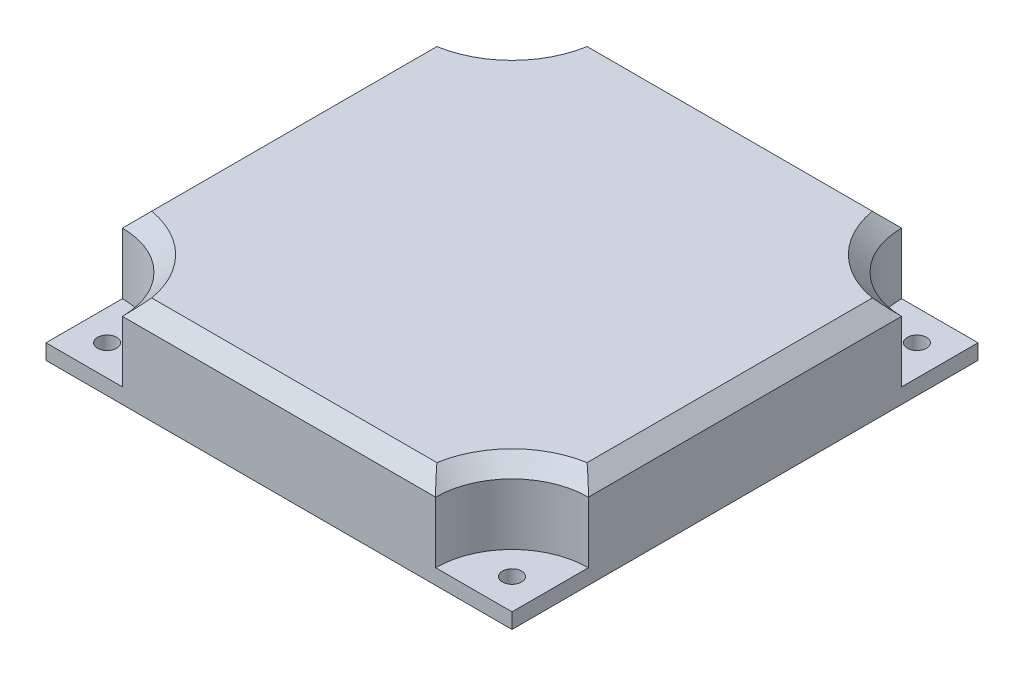
SolidWorks part; units mm, degrees
material "6061-T6 (SS)"
ref_plane "Front Plane" through (0, 0, 0) normal (0, 0, 1) x (1, 0, 0)
ref_plane "Top Plane" through (0, 0, 0) normal (0, 1, 0) x (1, 0, 0)
ref_plane "Right Plane" through (0, 0, 0) normal (1, 0, 0) x (0, 0, -1)
sketch "Sketch2" plane through (0, 0, 0) normal (0, 1, 0) x (1, 0, 0)
  line L1 (-30.5, -30.5) -> (30.5, -30.5)
  line L2 (-30.5, -30.5) -> (-30.5, 30.5)
  line L3 (-30.5, 30.5) -> (30.5, 30.5)
  line L4 (30.5, -30.5) -> (30.5, 30.5)
  line L5 (-30.5, -30.5) -> (30.5, 30.5) construction
  line L6 (-30.5, 30.5) -> (30.5, -30.5) construction
  point P0 (0, 0)
  dimension "D1" = 61
  dimension "D2" = 61
extrude "Boss-Extrude1" add sketch "Sketch2" along normal blind 12
ref_plane "Plane1" through (0, 0, 10.5) normal (0, 0, -1) x (-1, 0, 0)
ref_plane "Plane2" through (0, 0, 0) normal (1, 0, 0) x (0, 0, -1)
sketch "Sketch4" plane through (0, 12, 0) normal (0, 1, 0) x (1, 0, 0)
  line L5 (0, 0) -> (43.0078, 0) construction
  circle A1 centre (30.5, -30.5) radius 10
  circle A2 centre (-30.5, -30.5) radius 10
  circle A3 centre (-30.5, 30.5) radius 10
  circle A4 centre (30.5, 30.5) radius 10
  dimension "D1" = 20
extrude "Cut-Extrude3" cut sketch "Sketch4" against normal blind 10 contours A1 | A2 | A3 | A4
sketch "Sketch8" plane through (0, 0, 0) normal (0, -1, 0) x (1, 0, 0)
  line L12 (-18.6678, -28.5) -> (18.6678, -28.5)
  line L13 (-28.5, 18.6678) -> (-28.5, -18.6678)
  line L14 (18.6678, 28.5) -> (-18.6678, 28.5)
  line L15 (28.5, -18.6678) -> (28.5, 18.6678)
  line L16 (-18.6678, -28.5) -> (18.6678, -28.5)
  line L17 (-28.5, 18.6678) -> (-28.5, -18.6678)
  line L18 (18.6678, 28.5) -> (-18.6678, 28.5)
  line L19 (28.5, -18.6678) -> (28.5, 18.6678)
  arc A12 (28.5, -18.6678) -> (18.6678, -28.5) centre (30.5, -30.5) ccw
  arc A13 (-18.6678, -28.5) -> (-28.5, -18.6678) centre (-30.5, -30.5) ccw
  arc A14 (-28.5, 18.6678) -> (-18.6678, 28.5) centre (-30.5, 30.5) ccw
  arc A15 (18.6678, 28.5) -> (28.5, 18.6678) centre (30.5, 30.5) ccw
  arc A16 (28.5, -18.6678) -> (18.6678, -28.5) centre (30.5, -30.5) ccw
  arc A17 (-18.6678, -28.5) -> (-28.5, -18.6678) centre (-30.5, -30.5) ccw
  arc A18 (-28.5, 18.6678) -> (-18.6678, 28.5) centre (-30.5, 30.5) ccw
  arc A19 (18.6678, 28.5) -> (28.5, 18.6678) centre (30.5, 30.5) ccw
  dimension "D1" = 2
extrude "Cut-Extrude5" cut sketch "Sketch8" against normal blind 10
fillet "Fillet2" radius 2 8 edges at (30.5, 12, 0) (23.4289, 12, 23.4289) (0, 12, 30.5) (-23.4289, 12, 23.4289) (-30.5, 12, 0) (-23.4289, 12, -23.4289) (0, 12, -30.5) (23.4289, 12, -23.4289) profile chamfer
sketch "Sketch11" plane through (0, 2, 0) normal (0, 1, 0) x (1, 0, 0)
  line L0 (30.5, -26.5) -> (-30.5, -26.5) construction
  line L1 (30.5, -30.5) -> (30.5, -20.5) construction
  line L2 (-30.5, -20.5) -> (-30.5, -30.5) construction
  line L3 (26.5, -30.5) -> (26.5, 30.5) construction
  line L4 (20.5, -30.5) -> (30.5, -30.5) construction
  line L5 (20.5, 30.5) -> (30.5, 30.5) construction
  dimension "D1" = 4
  dimension "D2" = 4
hole_wizard "M3x0.5 Tapped Hole1" positions "Sketch13" profile "Sketch15" tap size "M3x0.5" standard "ANSI Metric"
sketch "Sketch13" plane through (0, 2, 0) normal (0, 1, 0) x (1, 0, 0)
  line L0 (30.5, -26.5) -> (-30.5, -26.5) construction
  line L1 (26.5, -30.5) -> (26.5, 30.5) construction
  point P0 (26.5, -26.5)
sketch "Sketch15" plane through (26.5, 2, 26.5) normal (1, 0, 0) x (0, 0, 1)
  line L0 (0, 0) -> (0, 8.2511)
  line L1 (0, 8.2511) -> (1.25, 7.5)
  line L2 (1.25, 7.5) -> (1.25, 0)
  line L5 (1.25, 0) -> (0, 0)
  line L10 (0, 8.2511) -> (-1.25, 7.5) construction
  line L11 (0, -6.35) -> (0, 107.95) construction
  dimension "Tap Drill Dia." = 2.5
  dimension "Tap Drill Depth" = 7.5
  dimension "Drill Angle" = 118
cosmetic thread "Hole Thread1" parameters "D1"=6, "D2"=3
mirror "Mirror1" about plane through (0, 0, 0) normal (0, 0, 1) of "M3x0.5 Tapped Hole1"
cosmetic thread "Hole Thread2" parameters "D1"=6, "D2"=3
mirror "Mirror2" about plane through (0, 0, 0) normal (1, 0, 0) of "Mirror1", "M3x0.5 Tapped Hole1"
cosmetic thread "Hole Thread3" parameters "D1"=6, "D2"=3
cosmetic thread "Hole Thread4" parameters "D1"=6, "D2"=3
fillet "Fillet3" radius 5 8 edges at (18.6678, 5, -28.5) (28.5, 5, -18.6678) (28.5, 5, 18.6678) (18.6678, 5, 28.5) (-18.6678, 5, 28.5) (-28.5, 5, 18.6678) (-18.6678, 5, -28.5) (-28.5, 5, -18.6678)
